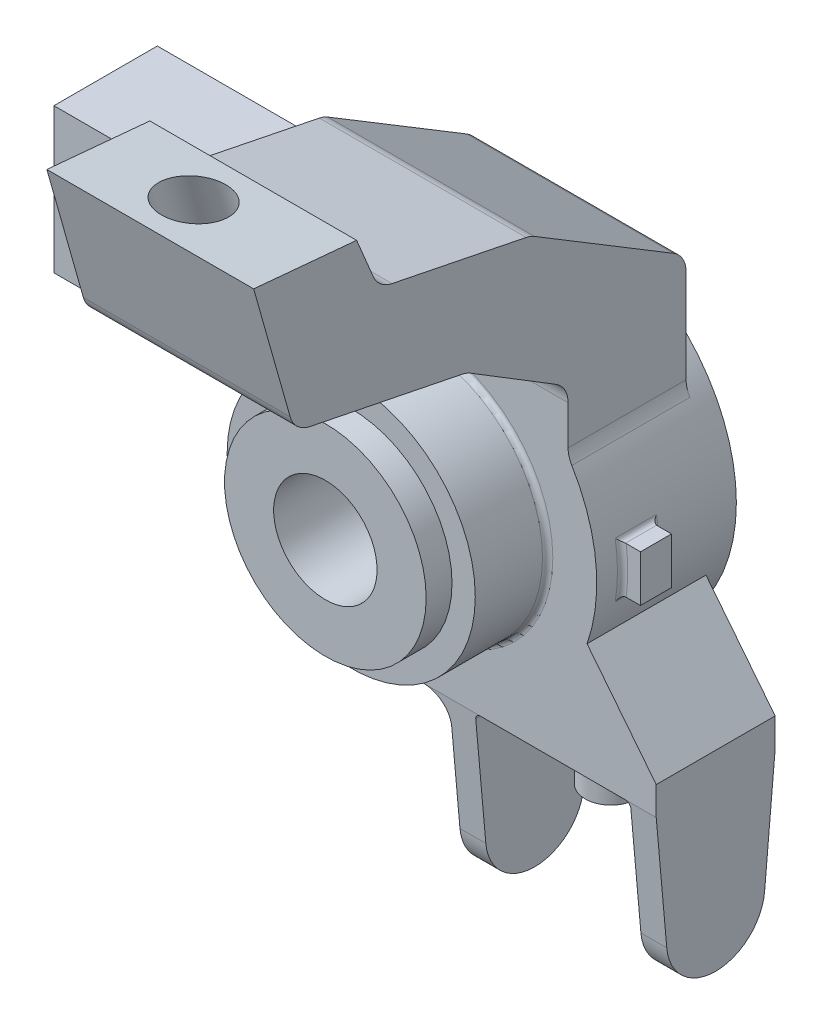
SolidWorks part; units mm, degrees
ref_plane "Front Plane" through (0, 0, 0) normal (0, 0, 1) x (1, 0, 0)
ref_plane "Top Plane" through (0, 0, 0) normal (0, 1, 0) x (1, 0, 0)
ref_plane "Right Plane" through (0, 0, 0) normal (1, 0, 0) x (0, 0, -1)
ref_axis "X-axis" through (-88.99, 0, 0) along (1, 0, 0)
ref_axis "Y-axis" through (0, 55, 0) along (0, -1, 0)
ref_axis "Z-axis" through (0, 0, -88.99) along (0, 0, 1)
sketch "Sketch1" plane through (0, 0, 0) normal (0, 0, 1) x (1, 0, 0)
  circle A0 centre (0, 0) radius 3.35
  dimension "D1" = 6.7
extrude "Boss-Extrude1" add sketch "Sketch1" along normal blind 2.7
sketch "Sketch2" plane through (0, 0, 2.7) normal (0, 0, 1) x (1, 0, 0)
  circle A0 centre (0, 0) radius 2.4
  dimension "D1" = 4.8
extrude "Boss-Extrude2" add sketch "Sketch2" along normal blind 1.4
sketch "Sketch3" plane through (0, 0, 4.1) normal (0, 0, 1) x (1, 0, 0)
  circle A0 centre (0, 0) radius 1.95
  dimension "D1" = 3.9
extrude "Boss-Extrude3" add sketch "Sketch3" along normal blind 0.5
hole_wizard "Ø2.0mm Dowel Hole1" positions "Sketch4" profile "Sketch5" hole size "Ø2.0" standard "ANSI Metric"
sketch "Sketch4" plane through (0, 0, 4.6) normal (0, 0, 1) x (1, 0, 0)
  point P0 (0, 0)
sketch "Sketch5" plane through (0, 0, 4.6) normal (1, 0, 0) x (0, -1, 0)
  line L0 (0, 0) -> (0, 52.9209)
  line L1 (0, 52.9209) -> (1, 52.32)
  line L2 (1, 52.32) -> (1, 0)
  line L5 (1, 0) -> (0, 0)
  line L10 (0, 52.9209) -> (-1, 52.32) construction
  line L11 (0, -6.35) -> (0, 107.95) construction
  dimension "Hole Dia." = 2
  dimension "Hole Depth" = 52.32
  dimension "Drill Angle" = 118
ref_plane "Plane1" through (0, 0, 0.4) normal (0, 0, -1) x (-1, 0, 0)
sketch "Sketch7" plane through (0, 0, 0.4) normal (0, 0, -1) x (-1, 0, 0)
  line L0 (2.1748, 2.45) -> (7.45, 2.45)
  line L1 (7.45, 2.45) -> (7.45, -0.35)
  line L2 (7.45, -0.35) -> (2.1748, -0.35)
  line L3 (2.1748, 2.45) -> (2.1748, -0.35)
  line L4 (0, 0) -> (0, 3.35) construction
  line L5 (0, 0) -> (0, -3.35) construction
  line L6 (0, 0) -> (3.35, 0) construction
  circle A1 centre (0, 0) radius 3.35 construction
  point P6 (0, 0)
  dimension "D1" = 3
  dimension "D2" = 2.8
  dimension "D3" = 4.1
extrude "Boss-Extrude4" add sketch "Sketch7" against normal blind 2
hole_wizard "Ø2.0mm Dowel Hole2" positions "Sketch8" profile "Sketch9" hole size "Ø2.0" standard "ANSI Metric"
sketch "Sketch8" plane through (0, 0, 0.4) normal (0, 0, -1) x (-1, 0, 0)
  line L0 (7.45, 2.45) -> (2.2847, 2.45) construction
  line L1 (7.45, -0.35) -> (7.45, 2.45) construction
  point P0 (5.95, 1.35)
  dimension "D1" = 1.1
  dimension "D2" = 1.5
sketch "Sketch9" plane through (-5.95, 1.35, 0.4) normal (1, 0, 0) x (0, 1, 0)
  line L0 (0, 0) -> (0, 52.6805)
  line L1 (0, 52.6805) -> (0.6, 52.32)
  line L2 (0.6, 52.32) -> (0.6, 0)
  line L5 (0.6, 0) -> (0, 0)
  line L10 (0, 52.6805) -> (-0.6, 52.32) construction
  line L11 (0, -6.35) -> (0, 107.95) construction
  dimension "Hole Dia." = 1.2
  dimension "Hole Depth" = 52.32
  dimension "Drill Angle" = 118
sketch "Sketch10" plane through (0, 0, 0.4) normal (0, 0, -1) x (-1, 0, 0)
  line L0 (0, 0) -> (0, -6.7605) construction
  line L1 (0, -3.35) -> (-4.5, -3.35)
  line L2 (-4.5, -3.35) -> (-4.5, -2.7967)
  line L3 (-4.5, -2.7967) -> (-3.1619, -1.1067)
  circle A0 centre (0, 0) radius 3.35 construction
  arc A1 (-3.1619, -1.1067) -> (0, -3.35) centre (0, 0) ccw
  point P10 (-3.1097, -1.1233)
  point P11 (-3.1619, -1.1067)
  point P12 (-3.1502, -1.1397)
  dimension "D2" = 4.5
extrude "Boss-Extrude5" add sketch "Sketch10" along direction (0, 0, 1) on the side against the normal up to surface (2.3 mm away) up to face at (2.4, 0, 2.7)
sketch "Sketch11" plane through (4.5, 0, 0) normal (1, 0, 0) x (0, 0, -1)
  line L0 (-1.55, -3.35) -> (-1.55, -5.55) construction
  line L1 (-2.7, -3.35) -> (-0.4, -3.35) construction
  line L2 (-2.7, -3.35) -> (-2.4962, -5.6344)
  line L3 (-0.4, -3.35) -> (-0.6038, -5.6344)
  line L4 (-2.7, -3.35) -> (-0.4, -3.35)
  arc A0 (-2.4962, -5.6344) -> (-0.6038, -5.6344) centre (-1.55, -5.55) ccw
  dimension "D2" = 1.9
  dimension "D1" = 2.2
extrude "Boss-Extrude6" add sketch "Sketch11" against normal blind 0.5
pattern_linear "LPattern1" count 2 spacing 3.5 along (-1, 0, 0) of "Boss-Extrude6"
sketch "Sketch12" plane through (0, -3.35, 0) normal (0, -1, 0) x (1, 0, 0)
  line L1 (4, 2.4962) -> (4, 0.6038) construction
  circle A0 centre (2.5, 1.5754) radius 0.5
  point P2 (0, 0)
  dimension "D1" = 1
  dimension "D2" = 1.5
extrude "Boss-Extrude7" add sketch "Sketch12" along normal blind 1
ref_plane "Plane2" through (0, 0, 1.6) normal (0, 0, -1) x (-1, 0, 0)
sketch "Sketch13" plane through (0, 0, 1.6) normal (0, 0, -1) x (-1, 0, 0)
  line L0 (-3.6951, -0.45) -> (-3.6951, 0.45)
  line L1 (-3.6951, 0.45) -> (-3.1831, 0.45)
  line L2 (-3.1831, 0.45) -> (-3.1831, -0.45)
  line L3 (-3.1831, -0.45) -> (-3.6951, -0.45)
  point P3 (-3.6951, 0)
  dimension "D1" = 0.9
extrude "Boss-Extrude8" add sketch "Sketch13" against normal blind 0.6
ref_plane "Plane3" through (2.7951, 0, 0) normal (1, 0, 0) x (0, 0, -1)
sketch "Sketch14" plane through (2.7951, 0, 0) normal (1, 0, 0) x (0, 0, -1)
  line L0 (-0.4176, 0.9707) -> (-0.4176, 4.0826)
  line L1 (-2.7, 0.9707) -> (-2.7, 3.0284)
  line L2 (-2.7, 2.4) -> (-2.7, -2.4) construction
  line L3 (-2.7, 3.35) -> (-2.7, -3.35) construction
  line L4 (-2.7, 3.0284) -> (-4.6607, 4.2308)
  line L5 (-4.6607, 4.2308) -> (-7.9932, 4.9048)
  line L6 (-7.9932, 4.9048) -> (-8.7819, 7.6955)
  line L7 (-8.7819, 7.6955) -> (-6.7902, 7.5128)
  line L11 (-2.7, 0.9707) -> (-0.4176, 0.9707)
  line L12 (-6.7902, 7.5128) -> (-6.3663, 6.4987)
  line L13 (-6.3663, 6.4987) -> (-3.4258, 5.904)
  line L14 (-3.4258, 5.904) -> (-0.4176, 4.0826)
  point P8 (0, 0)
  dimension "D3" = 2.3
  dimension "D4" = 3.4
  dimension "D5" = 2.9
  dimension "D6" = 2
  dimension "D7" = 3
extrude "Boss-Extrude9" add sketch "Sketch14" against normal blind 4
sketch "Sketch6" plane through (0, 0, 0) normal (0, 0, -1) x (-1, 0, 0)
  circle A0 centre (0, 0) radius 2.1
  dimension "D1" = 4.2
extrude "Cut-Extrude1" cut sketch "Sketch6" against normal blind 2
sketch "Sketch17" plane through (0, 6.8321, -0.6269) normal (0, 0.9958, -0.0914) x (1, 0, 0)
  circle A0 centre (0.6306, -8.4413) radius 0.625
  dimension "D1" = 1.25
extrude "Cut-Extrude2" cut sketch "Sketch17" along direction (0, -0.9623, -0.2719) on the side against the normal blind 2
fillet "Fillet1" radius 0.1 8 edges at (2.4, 0, 2.7) (-2.1, 0, 2) (3.3196, 0.45, 1.9) (3.35, 0, 2.2) (3.3196, -0.45, 1.9) (3.35, 0, 1.6) (4, -3.35, 1.55) (1, -3.35, 1.55)
fillet "Fillet2" radius 2.7 1 edges at (-2.2847, 2.45, 1.4)
fillet "Fillet3" radius 0.5 9 edges at (0.7951, 4.0826, 0.4176) (0.7951, 5.904, 3.4258) (0.7951, 6.4987, 6.3663) (0.7951, 4.9048, 7.9932) (0.7951, 4.2308, 4.6607) (0.7951, 3.0284, 2.7) (2.7951, 1.8465, 1.5588) (0.5, -3.35, 1.55) (-3.3317, -0.35, 1.4)
sketch "Sketch18" plane through (0, 0, 0) normal (0, 0, -1) x (-1, 0, 0)
  circle A0 centre (0, 0) radius 2.8
  dimension "D1" = 5.6
extrude "Cut-Extrude3" cut sketch "Sketch18" against normal blind 0.8
sketch "Sketch19" plane through (0, 0, 0.8) normal (0, 0, -1) x (-1, 0, 0)
  line L0 (2.0904, 0.2008) -> (2.7872, 0.2678)
  line L1 (2.033, -0.5262) -> (2.7107, -0.7017)
  circle A0 centre (0, 0) radius 2.1 construction
  arc A1 (2.033, -0.5262) -> (2.0904, 0.2008) centre (0, 0) ccw
  circle A3 centre (0, 0) radius 2.8 construction
  arc A4 (2.7107, -0.7017) -> (2.7872, 0.2678) centre (0, 0) ccw
  dimension "D1" = 20
extrude "Boss-Extrude10" add sketch "Sketch19" along normal blind 0.8
